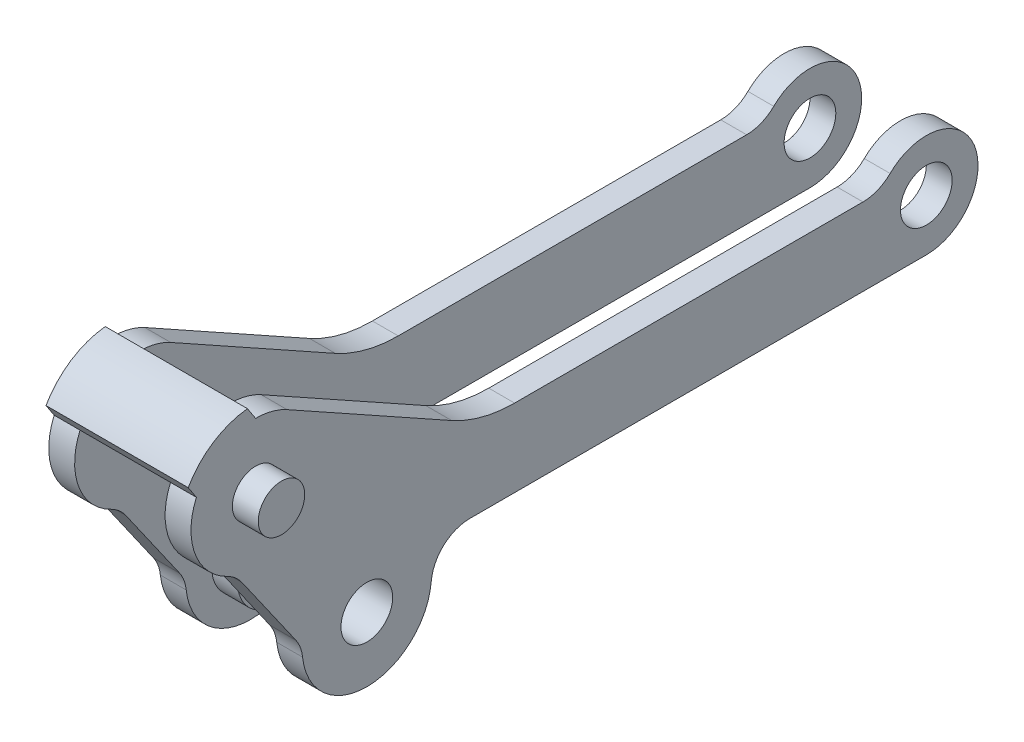
SolidWorks part; units mm, degrees
ref_plane "前视基准面" through (0, 0, 0) normal (0, 0, 1) x (1, 0, 0)
ref_plane "上视基准面" through (0, 0, 0) normal (0, 1, 0) x (1, 0, 0)
ref_plane "右视基准面" through (0, 0, 0) normal (1, 0, 0) x (0, 0, -1)
other "Configuration Table"
sketch "草图1" plane through (0, 0, 0) normal (1, 0, 0) x (0, 0, -1)
  line L1 (0, 0) -> (44.2012, 0)
  line L2 (0, 0) -> (4.2012, -6)
  line L3 (4.2012, -6) -> (44.2012, -6)
  line L4 (44.2012, 0) -> (44.2012, -6)
  line L5 (-10.9556, 1.6987) -> (-4.4024, 6.2873)
  line L6 (-10.9556, 1.6987) -> (-2.352, -10.5886)
  line L7 (-2.352, -10.5886) -> (4.2012, -6)
  line L8 (-4.4024, 6.2873) -> (4.2012, -6)
  circle A0 centre (-7.679, 3.993) radius 5
  circle A1 centre (0.9246, -8.2943) radius 5
  circle A3 centre (44.2012, -2) radius 4
  circle A4 centre (-7.679, 3.993) radius 2
  circle A5 centre (44.2012, -2) radius 2
  circle A6 centre (0.9246, -8.2943) radius 2
  circle A7 centre (0.9246, -8.2943) radius 3
  dimension "D5" = 10
  dimension "D6" = 10
  dimension "D8" = 8
  dimension "D9" = 4
  dimension "D10" = 6
  dimension "D1" = 125
  dimension "D2" = 40
  dimension "D3" = 6
  dimension "D4" = 8
  dimension "D7" = 15
extrude "凸台-拉伸1" add sketch "草图1" along normal blind 2 contours A3 L1 L2 A1 L3 | A0 | L8 L5 L6 L7 | A1 | A3 region at (0, -2.9524, -21.636)
extrude "凸台-拉伸2" add sketch "草图1<4>" against normal blind 2 contours A7
sketch "草图1<4>" plane through (0, 0, 0) normal (1, 0, 0) x (0, 0, -1) same geometry as "草图1"
extrude "切除-拉伸1" cut sketch "草图1<3>" along normal through all both and the other way through all contours A4 | A6 | A5
sketch "草图1<3>" plane through (0, 0, 0) normal (1, 0, 0) x (0, 0, -1) same geometry as "草图1"
fillet "圆角1" radius 3 5 edges at (1, 0, -40.7371) (1, -8.1312, 4.0727) (1, -0.7588, 9.2349) (1, -6, -5.3672) (1, 0, 0)
sketch "草图2" plane through (2, 0, 0) normal (1, 0, 0) x (0, 0, -1)
  circle A0 centre (-7.679, 3.993) radius 2
  circle A1 centre (-7.679, 3.993) radius 1.8
  circle A2 centre (-7.679, 3.993) radius 2 construction
  dimension "D1" = 3.6
extrude "凸台-拉伸3" add sketch "草图2" against normal up to surface (2 mm away) contours A0 up to face at (0, 3.993, 5.679)
extrude "凸台-拉伸4" add sketch "草图2<3>" along normal blind 2 contours A1 region at (2, 3.993, 7.679)
sketch "草图2<3>" plane through (2, 0, 0) normal (1, 0, 0) x (0, 0, -1) same geometry as "草图2"
ref_plane "基准面1" through (-3.5, 0, 0) normal (-1, 0, 0) x (0, 0, 1)
sketch "草图4" plane through (2, 0, 0) normal (1, 0, 0) x (0, 0, -1)
  line L0 (-5.2448, 8.3604) -> (9.7552, 0)
  line L1 (1.5617, 0) -> (39.3023, 0) construction
  line L5 (-5.2448, 0) -> (-5.2448, 8.3604)
  line L6 (-5.2448, 0) -> (9.7552, 0)
  arc A2 (-2.6817, 3.8298) -> (-9.8744, -0.4993) centre (-7.679, 3.993) ccw construction
  dimension "D1" = 15
extrude "凸台-拉伸6" add sketch "草图4" against normal blind 2
sketch "草图3" plane through (2, 0, 0) normal (1, 0, 0) x (0, 0, -1)
  line L0 (-7.679, 3.993) -> (-16.6015, 16.7356) construction
  line L1 (-8.7342, -1.4739) -> (-4.5734, -7.416) construction
  line L2 (-19.3045, 5.993) -> (3.1525, 5.993) construction
  line L7 (-7.679, 8.993) -> (-12.2616, 5.993) construction
  line L8 (-12.2616, 5.993) -> (-13.2566, 7.5129)
  line L9 (9.7552, 0) -> (39.3023, 0) construction
  line L10 (-13.2566, 7.5129) -> (-8.6741, 10.5129) construction
  line L11 (-8.6741, 10.5129) -> (-7.679, 8.993)
  circle A0 centre (-7.679, 3.993) radius 5
  arc A1 (-5.2448, 8.3604) -> (-9.8744, -0.4993) centre (-7.679, 3.993) ccw construction
  circle A2 centre (-7.679, 3.993) radius 2
  circle A3 centre (0.9246, -8.2943) radius 2 construction
  circle A4 centre (-7.679, 3.993) radius 6
  point P7 (-14.0836, 13.1397)
  arc M18 (-5.2448, 8.3604) -> (-9.8744, -0.4993) centre (-7.679, 3.993) ccw
  dimension "D1" = 12
extrude "凸台-拉伸5" add sketch "草图3" against normal up to surface (5.5 mm away) contours L11 A4 L8 M18 region at (2, 8.3868, 10.5555) up to plane "基准面1"
fillet "圆角3" radius 10 1 edges at (1, 0, -9.7552)
mirror "镜向1" about plane through (-3.5, 0, 0) normal (-1, 0, 0) of bodies 111
